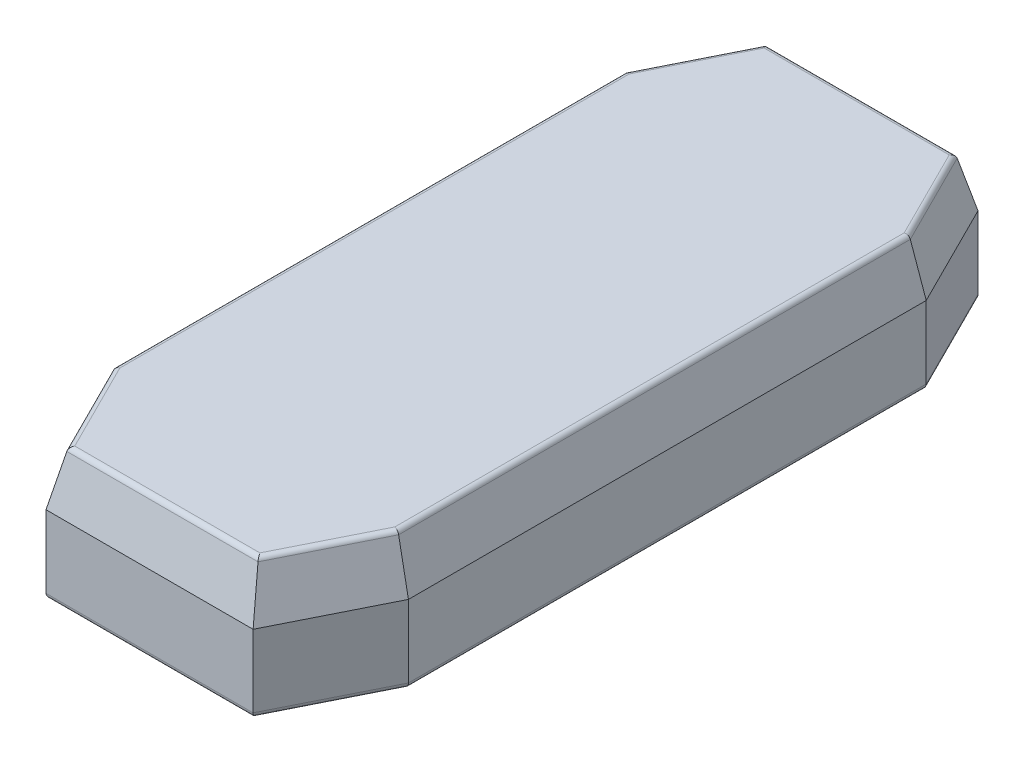
SolidWorks part; units mm, degrees
ref_plane "Front Plane" through (0, 0, 0) normal (0, 0, 1) x (1, 0, 0)
ref_plane "Top Plane" through (0, 0, 0) normal (0, 1, 0) x (1, 0, 0)
ref_plane "Right Plane" through (0, 0, 0) normal (1, 0, 0) x (0, 0, -1)
sketch "Sketch1" plane through (0, 0, 0) normal (0, 1, 0) x (1, 0, 0)
  line L0 (-7.62, 12.7) -> (-5.08, 17.78)
  line L1 (-5.08, 17.78) -> (5.08, 17.78)
  line L2 (-7.62, 12.7) -> (-7.62, -12.7)
  line L3 (-5.08, -17.78) -> (5.08, -17.78)
  line L4 (7.62, 12.7) -> (7.62, -12.7)
  line L5 (-7.62, 17.78) -> (7.62, -17.78) construction
  line L6 (-7.62, -17.78) -> (7.62, 17.78) construction
  line L7 (5.08, 17.78) -> (7.62, 12.7)
  line L8 (5.08, -17.78) -> (7.62, -12.7)
  line L9 (-7.62, -12.7) -> (-5.08, -17.78)
  point P0 (0, 0)
  dimension "D1" = 15.24
  dimension "D2" = 35.56
  dimension "D3" = 2.54
  dimension "D4" = 5.08
  dimension "D5" = 2.54
  dimension "D6" = 5.08
  dimension "D7" = 2.54
  dimension "D8" = 5.08
  dimension "D9" = 5.08
  dimension "D10" = 2.54
extrude "Boss-Extrude1" add sketch "Sketch1" along normal blind 2.54 draft 15
sketch "Stem" plane through (0, 0, 0) normal (0, -1, 0) x (1, 0, 0)
  line L1 (-0.5625, 2.075) -> (0.5625, 2.075)
  line L2 (-0.5625, 2.075) -> (-0.5625, -2.075)
  line L3 (-0.5625, -2.075) -> (0.5625, -2.075)
  line L4 (0.5625, 2.075) -> (0.5625, -2.075)
  line L5 (-0.5625, 2.075) -> (0.5625, -2.075) construction
  line L6 (-0.5625, -2.075) -> (0.5625, 2.075) construction
  line L7 (2.0625, 0.6625) -> (-2.0625, 0.6625)
  line L8 (2.0625, 0.6625) -> (2.0625, -0.6625)
  line L9 (2.0625, -0.6625) -> (-2.0625, -0.6625)
  line L10 (-2.0625, 0.6625) -> (-2.0625, -0.6625)
  line L11 (2.0625, 0.6625) -> (-2.0625, -0.6625) construction
  line L12 (2.0625, -0.6625) -> (-2.0625, 0.6625) construction
  line L13 (-2.5, 2.5) -> (2.5, 2.5)
  line L14 (-3, 2) -> (-3, -2)
  line L15 (-2.5, -2.5) -> (2.5, -2.5)
  line L16 (3, 2) -> (3, -2)
  line L17 (-3, 2.5) -> (3, -2.5) construction
  line L18 (-3, -2.5) -> (3, 2.5) construction
  arc A0 (-3, -2) -> (-2.5, -2.5) centre (-2.5, -2) ccw
  arc A1 (-2.5, 2.5) -> (-3, 2) centre (-2.5, 2) ccw
  arc A2 (2.5, -2.5) -> (3, -2) centre (2.5, -2) ccw
  arc A3 (2.5, 2.5) -> (3, 2) centre (2.5, 2) cw
  point P0 (0, 0)
  point P6 (0, 0)
  point P11 (0, 0)
  dimension "D7" = 0.5
  dimension "D1" = 4.15
  dimension "D2" = 1.125
  dimension "D3" = 1.325
  dimension "D4" = 4.125
  dimension "D5" = 5
  dimension "D6" = 6
extrude "Boss-Extrude2" add sketch "Stem" along normal blind 3.8 contours A3 L13 A1 L14 A0 L15 A2 L16 L10 L7 L2 L1 L4 L8 L9 L3 region at (0, 0, 2.4219)
fillet "Fillet2" radius 0.1 8 edges at (-2.8536, -3.8, -2.3536) (-3, -3.8, 0) (-2.8536, -3.8, 2.3536) (0, -3.8, 2.5) (2.8536, -3.8, 2.3536) (3, -3.8, 0) (2.8536, -3.8, -2.3536) (0, -3.8, -2.5)
chamfer "Chamfer1" distance 0.2 angle 45 11 edges at (-0.5625, -3.8, -1.3688) (-1.3125, -3.8, -0.6625) (-2.0625, -3.8, 0) (0.5625, -3.8, -1.3688) (1.3125, -3.8, -0.6625) (2.0625, -3.8, 0) (1.3125, -3.8, 0.6625) (0.5625, -3.8, 1.3687) (0, -3.8, 2.075) (-0.5625, -3.8, 1.3687) (-1.3125, -3.8, 0.6625)
sketch "Sketch3" plane through (0, 0, 0) normal (0, -1, 0) x (1, 0, 0)
  line L0 (-7.62, 12.7) -> (-7.62, -12.7)
  line L1 (-7.62, -12.7) -> (-5.08, -17.78)
  line L2 (-5.08, -17.78) -> (5.08, -17.78)
  line L3 (5.08, -17.78) -> (7.62, -12.7)
  line L4 (7.62, -12.7) -> (7.62, 12.7)
  line L5 (7.62, 12.7) -> (5.08, 17.78)
  line L6 (5.08, 17.78) -> (-5.08, 17.78)
  line L7 (-5.08, 17.78) -> (-7.62, 12.7)
  line L44 (-6.35, -12.4002) -> (-4.2951, -16.51)
  line L45 (-4.2951, -16.51) -> (4.2951, -16.51)
  line L46 (4.2951, -16.51) -> (6.35, -12.4002)
  line L47 (6.35, -12.4002) -> (6.35, 12.4002)
  line L48 (6.35, 12.4002) -> (4.2951, 16.51)
  line L49 (4.2951, 16.51) -> (-4.2951, 16.51)
  line L50 (-4.2951, 16.51) -> (-6.35, 12.4002)
  line L51 (-6.35, 12.4002) -> (-6.35, -12.4002)
  line L52 (-6.35, -12.4002) -> (-4.2951, -16.51)
  line L53 (-4.2951, -16.51) -> (4.2951, -16.51)
  line L54 (4.2951, -16.51) -> (6.35, -12.4002)
  line L55 (6.35, -12.4002) -> (6.35, 12.4002)
  line L56 (6.35, 12.4002) -> (4.2951, 16.51)
  line L57 (4.2951, 16.51) -> (-4.2951, 16.51)
  line L58 (-4.2951, 16.51) -> (-6.35, 12.4002)
  line L59 (-6.35, 12.4002) -> (-6.35, -12.4002)
  dimension "D1" = 1.27
extrude "Boss-Extrude3" add sketch "Sketch3" along normal blind 3.8
fillet "Fillet3" radius 0.25 16 edges at (0, -3.8, -16.51) (5.3225, -3.8, -14.4551) (6.35, -3.8, 0) (5.3225, -3.8, 14.4551) (0, -3.8, 16.51) (-5.3225, -3.8, 14.4551) (-6.35, -3.8, 0) (-5.3225, -3.8, -14.4551) (0, -3.8, 17.78) (6.35, -3.8, 15.24) (7.62, -3.8, 0) (6.35, -3.8, -15.24) (0, -3.8, -17.78) (-6.35, -3.8, -15.24) (-7.62, -3.8, 0) (-6.35, -3.8, 15.24)
fillet "Fillet5" radius 0.5 16 edges at (0, 0, 2.5) (-2.8536, 0, 2.3536) (-3, 0, 0) (-2.8536, 0, -2.3536) (0, 0, -2.5) (2.8536, 0, -2.3536) (3, 0, 0) (2.8536, 0, 2.3536) (-5.3225, 0, 14.4551) (0, 0, 16.51) (5.3225, 0, 14.4551) (6.35, 0, 0) (5.3225, 0, -14.4551) (0, 0, -16.51) (-5.3225, 0, -14.4551) (-6.35, 0, 0)
fillet "Fillet6" radius 0.1 12 edges at (-1.3125, 0, 0.6625) (-0.5625, 0, 1.3687) (0, 0, 2.075) (0.5625, 0, 1.3687) (1.3125, 0, 0.6625) (2.0625, 0, 0) (1.3125, 0, -0.6625) (0.5625, 0, -1.3688) (0, 0, -2.075) (-0.5625, 0, -1.3688) (-1.3125, 0, -0.6625) (-2.0625, 0, 0)
fillet "Fillet7" radius 0.25 8 edges at (5.7994, 2.54, -14.8194) (6.9394, 2.54, 0) (5.7994, 2.54, 14.8194) (0, 2.54, 17.0994) (-5.7994, 2.54, 14.8194) (-6.9394, 2.54, 0) (-5.7994, 2.54, -14.8194) (0, 2.54, -17.0994)
sketch "Sketch4" plane through (0, 2.54, 0) normal (0, 1, 0) x (1, 0, 0)
  line L24 (5.7316, -12.2542) -> (5.7316, 12.2542)
  line L25 (5.7316, 12.2542) -> (3.9129, 15.8916)
  line L26 (3.9129, 15.8916) -> (-3.9129, 15.8916)
  line L27 (-3.9129, 15.8916) -> (-5.7316, 12.2542)
  line L28 (-5.7316, 12.2542) -> (-5.7316, -12.2542)
  line L29 (-5.7316, -12.2542) -> (-3.9129, -15.8916)
  line L30 (-3.9129, -15.8916) -> (3.9129, -15.8916)
  line L31 (3.9129, -15.8916) -> (5.7316, -12.2542)
  line L32 (5.7316, -12.2542) -> (5.7316, 12.2542)
  line L33 (5.7316, 12.2542) -> (3.9129, 15.8916)
  line L34 (3.9129, 15.8916) -> (-3.9129, 15.8916)
  line L35 (-3.9129, 15.8916) -> (-5.7316, 12.2542)
  line L36 (-5.7316, 12.2542) -> (-5.7316, -12.2542)
  line L37 (-5.7316, -12.2542) -> (-3.9129, -15.8916)
  line L38 (-3.9129, -15.8916) -> (3.9129, -15.8916)
  line L39 (3.9129, -15.8916) -> (5.7316, -12.2542)
  dimension "D1" = 1.016
